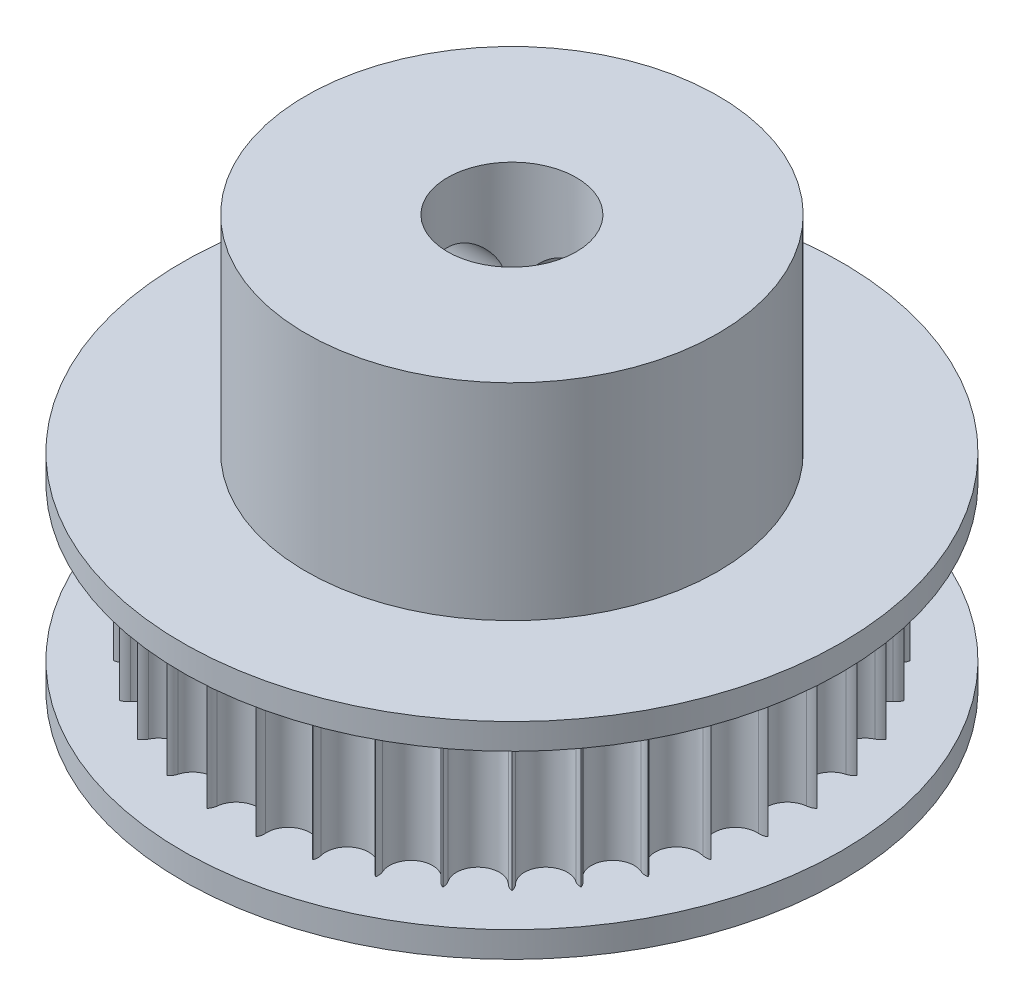
SolidWorks part; units mm, degrees
ref_plane "Front plan" through (0, 0, 0) normal (0, 0, 1) x (1, 0, 0)
ref_plane "Top plan" through (0, 0, 0) normal (0, 1, 0) x (1, 0, 0)
ref_plane "Right plan" through (0, 0, 0) normal (1, 0, 0) x (0, 0, -1)
sketch "Skica2" plane through (0, 0, 0) normal (0, 0, 1) x (1, 0, 0)
  line L0 (8, 8.5) -> (2.5, 8.5)
  line L1 (2.5, 8.5) -> (2.5, -8.5)
  line L2 (2.5, -8.5) -> (6.11, -8.5)
  line L3 (0, -8.5) -> (0, 8.5) construction
  line L4 (0, 8.5) -> (2.5, 8.5)
  line L5 (0, -8.5) -> (2.5, -8.5)
  line L6 (6.11, -8.5) -> (6.11, -7.5)
  line L7 (12.8, -0.5) -> (11.15, -0.5)
  line L8 (11.15, -0.5) -> (11.15, -6.5)
  line L9 (12.8, -0.5) -> (12.8, 0.5)
  line L12 (12.8, -7.5) -> (6.11, -7.5)
  line L13 (12.8, 0.5) -> (8, 0.5)
  line L14 (12.8, -7.5) -> (12.8, -6.5)
  line L15 (11.15, -6.5) -> (12.8, -6.5)
  line L16 (8, 0.5) -> (8, 8.5)
  point P6 (9.455, -7.5)
  point P7 (0, 0)
  dimension "D2" = 1
  dimension "D6" = 25.6
  dimension "D3" = 22.3
  dimension "D1" = 5
  dimension "D8" = 17
  dimension "D4" = 1
  dimension "D7" = 16
  dimension "D9" = 8
revolve "Revolute" add sketch "Skica2" angle 360 about L3 region at (6.3138, -0.7046, 0)
sketch "Sketch2" plane through (0, -0.5, 0) normal (0, -1, 0) x (1, 0, 0)
  line L0 (0, 0) -> (0, 10.7023) construction
  line L1 (0, 0) -> (3.7597, 10.497) construction
  line L3 (0, 0) -> (-2.1589, 10.939) construction
  circle A1 centre (0, 0) radius 9.8663 construction
  circle A2 centre (0, 0) radius 10.65 construction
  arc A3 (-0.8317, 10.6175) -> (0.8317, 10.6175) centre (0, 10.7023) ccw
  arc A7 (-1.3915, 11.0628) -> (-2.1589, 10.939) centre (0, 0) ccw
  arc A8 (0, 12.5893) -> (2.1589, 10.939) centre (0.5977, 11.134) cw
  circle A9 centre (0, 0) radius 11.15 construction
  arc A10 (1.3915, 11.0628) -> (2.1589, 10.939) centre (0, 0) cw
  arc A11 (1.3915, 11.0628) -> (0.8317, 10.6175) centre (1.3291, 10.5667) ccw
  arc A12 (0, 12.5893) -> (-2.1589, 10.939) centre (-0.5977, 11.134) ccw
  arc A13 (-1.3915, 11.0628) -> (-0.8317, 10.6175) centre (-1.3291, 10.5667) cw
  circle M8 centre (0, 0) radius 11.15
  dimension "D2" = 1
  dimension "D4" = 0.836
  dimension "D6" = 22.3
  dimension "D3" = 1.5733
extrude "Cut-Extrude1" cut sketch "Sketch2" along normal up to surface (6 mm away) contours A8 M8 | A11 A3 M8 region at (0, -0.5, 10.6043) region at (0, -0.5, 11.8034) up to face at (12.8, -6.5, 0)
pattern_circular "CirPattern1" count 36 over 360 about axis through (0, -8.5, 0) along (0, -1, 0) of "Cut-Extrude1" reverse direction yes
sketch "Sketch3" plane through (0, 0, 0) normal (1, 0, 0) x (0, 0, -1)
  line L0 (0, 8.5) -> (0, 0.5) construction
  line L1 (2.5, 8.5) -> (-2.5, 8.5) construction
  circle A0 centre (0, 4.5) radius 1.65
  dimension "D1" = 3.3
extrude "Cut-Extrude2" cut sketch "Sketch3" against normal up to next
sketch "Sketch4" plane through (0, 0, 0) normal (0, 0, 1) x (1, 0, 0)
  line L0 (0, 8.5) -> (0, -0.5) construction
  line L1 (12.8, 8.5) -> (-12.8, 8.5) construction
  line L2 (-0.8317, -0.5) -> (0.8317, -0.5) construction
  circle A0 centre (0, 4) radius 1.65
  dimension "D1" = 3.3
extrude "Cut-Extrude3" cut sketch "Sketch4" against normal up to next
chamfer "Chamfer1" distance 1 angle 45 1 edges at (6.11, -7.5, 0)
equation "\"`\"=2"
equation "\"D6@Sketch2\"= \"D3@Skica2\""
